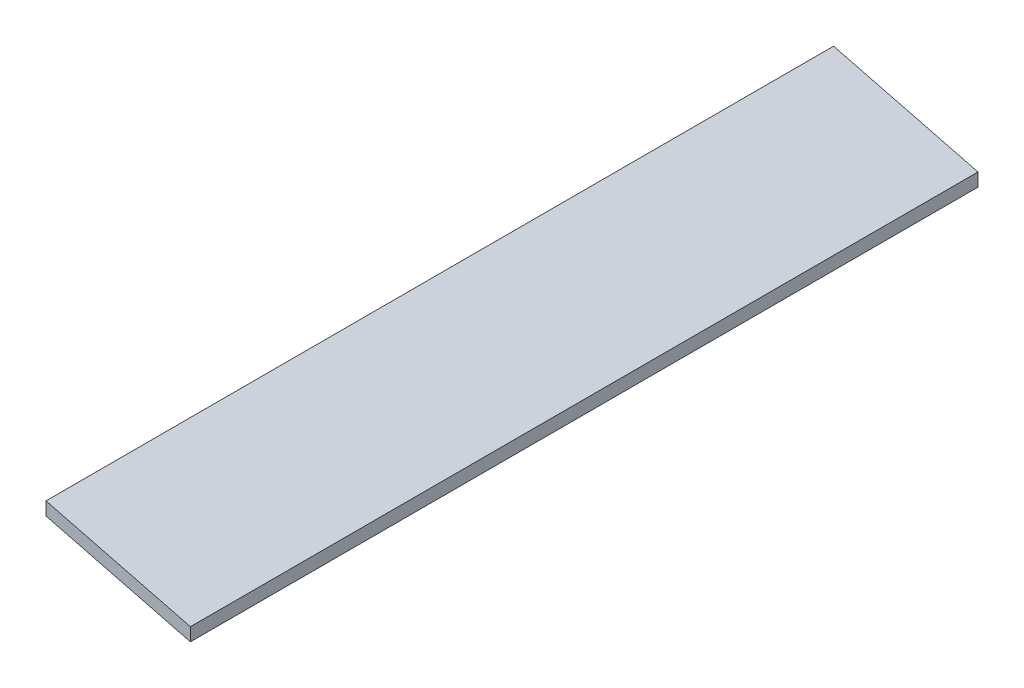
SolidWorks part; units mm, degrees
ref_plane "Plan de face" through (0, 0, 0) normal (0, 0, 1) x (1, 0, 0)
ref_plane "Plan de dessus" through (0, 0, 0) normal (0, 1, 0) x (1, 0, 0)
ref_plane "Plan de droite" through (0, 0, 0) normal (1, 0, 0) x (0, 0, -1)
sketch "Esquisse1" plane through (0, 0, 0) normal (0, 0, 1) x (1, 0, 0)
  line L0 (120, 155) -> (10, 183)
  line L1 (10, 183) -> (10, 173)
  line L2 (10, 183) -> (10, 0) construction
  line L3 (10, 173) -> (120, 145)
  line L4 (120, 0) -> (120, 155) construction
  line L5 (120, 145) -> (120, 155)
  dimension "D1" = 10
extrude "Boss.-Extru.1" add sketch "Esquisse1" against normal blind 600
